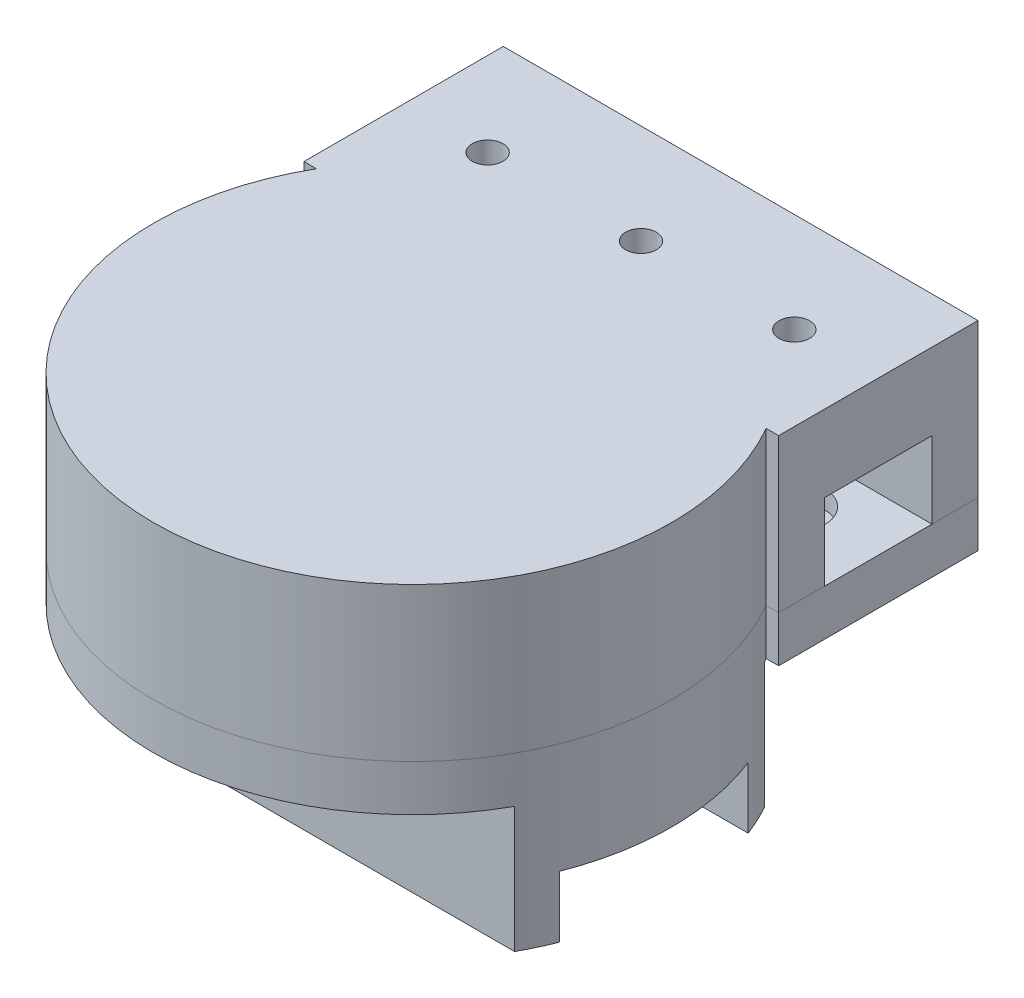
SolidWorks part; units mm, degrees
note: The reader was unsure of these and kept them because the rebuilt part matched: shared geometry of "Sketch1<4>", "Sketch1<7>", "Sketch1<9>", "Sketch3<5>", "Sketch11<4>".
ref_plane "Front Plane" through (0, 0, 0) normal (0, 0, 1) x (1, 0, 0)
ref_plane "Top Plane" through (0, 0, 0) normal (0, 1, 0) x (1, 0, 0)
ref_plane "Right Plane" through (0, 0, 0) normal (1, 0, 0) x (0, 0, -1)
sketch "Sketch1" plane through (0, 0, 0) normal (0, 1, 0) x (1, 0, 0)
  line L0 (-12.478, 11.3978) -> (12.478, 11.3978)
  line L1 (12.478, 11.3978) -> (12.478, 18.3978)
  line L2 (12.478, 18.3978) -> (-12.478, 18.3978)
  line L3 (-12.478, 18.3978) -> (-12.478, 11.3978)
  line L4 (-15.478, 8.3978) -> (15.478, 8.3978)
  line L5 (15.478, 8.3978) -> (15.478, 21.3978)
  line L6 (15.478, 21.3978) -> (-15.478, 21.3978)
  line L7 (-15.478, 21.3978) -> (-15.478, 8.3978)
  line L8 (-9.478, 18.3978) -> (-9.478, 21.3978)
  line L9 (9.478, 18.3978) -> (9.478, 21.3978)
  line L10 (-12.478, 18.3978) -> (-15.478, 18.3978)
  line L11 (-12.478, 11.3978) -> (-15.478, 11.3978)
  line L12 (12.478, 11.3978) -> (15.478, 11.3978)
  line L13 (12.478, 18.3978) -> (15.478, 18.3978)
  line L14 (0, 0) -> (0, 50.4739) construction
  line L15 (15.478, 21.3978) -> (15.478, 74.3978)
  line L16 (15.478, 74.3978) -> (-15.478, 74.3978)
  line L17 (-15.478, 74.3978) -> (-15.478, 21.3978)
  line L18 (-9.478, 21.3978) -> (-9.478, 71.3978)
  line L19 (-9.478, 71.3978) -> (9.478, 71.3978)
  line L20 (9.478, 71.3978) -> (9.478, 21.3978)
  circle A0 centre (0, 0) radius 16.9
  circle A1 centre (0, 0) radius 8.3978 construction
  circle A2 centre (0, 0) radius 13.9
  circle A3 centre (0, 0) radius 2
  point P17 (0, 21.3978)
  dimension "D1" = 3
  dimension "D3" = 3
  dimension "D6" = 27.8
  dimension "D11" = 4
  dimension "D4" = 3
  dimension "D5" = 3
  dimension "D7" = 11.3978
  dimension "D8" = 7
  dimension "D9" = 3
  dimension "D10" = 50
extrude "Boss-Extrude1" add sketch "Sketch1" against normal blind 5 contours L10 L2 L8 L6 L7 | A0 L0 L11 L7 L4 | A0 L4 L5 L12 L0 | L2 L13 L5 L6 L9 | A2 L4 A0 | A2 L0 A0 L4 | A2 L4 A0 L0 | L3
extrude "Boss-Extrude2" add sketch "Sketch1<4>" along normal blind 5 contours A2 L4 A0 | A1 | L4 A2 A1 | L4 A2 L0 | L0 A2 | A2 L0 A0 | A2 L0 A0 L4 | A2 L4 A0 L0 | A0 L4 L5 L6 L9 L2 L1 L0 | L2 L9 L6 L8 | A0 L0 L3 L2 L8 L6 L7 L4 | L14 L4 A2 L0 | L14 L0 A2 | L14 A2 L0 A0 | L14 A0 L0 L1 L2 | L13 L1 L12 L5
sketch "Sketch1<4>" plane through (0, 0, 0) normal (0, 1, 0) x (1, 0, 0) same geometry as "Sketch1"
sketch "Sketch3" plane through (0, -5, 0) normal (0, -1, 0) x (1, 0, 0)
  line L1 (-15.478, -8.3978) -> (-14.6659, -8.3978) construction
  line L2 (15.478, -21.3978) -> (9.478, -21.3978) construction
  line L3 (-9.478, -21.3978) -> (-15.478, -21.3978) construction
  line L4 (-15.478, -8.3978) -> (-14.6659, -8.3978)
  line L5 (14.6659, -8.3978) -> (15.478, -8.3978) construction
  line L6 (14.6659, -8.3978) -> (15.478, -8.3978)
  line L12 (15.478, -21.3978) -> (15.478, -8.3978)
  line L13 (15.478, -21.3978) -> (9.478, -21.3978)
  line L14 (-9.478, -21.3978) -> (-15.478, -21.3978)
  line L16 (9.478, -21.3978) -> (-9.478, -21.3978)
  line L17 (-15.478, -21.3978) -> (-15.478, -8.3978)
  arc A2 (14.6659, -8.3978) -> (-14.6659, -8.3978) centre (0, 0) ccw construction
  arc A3 (14.6659, -8.3978) -> (-14.6659, -8.3978) centre (0, 0) ccw
  circle A4 centre (0, 0) radius 5.35
  circle A5 centre (0, 0) radius 2 construction
  dimension "D2" = 10.7
extrude "Boss-Extrude6" add sketch "Sketch1<7>" along normal up to surface (5 mm away) and the other way blind 2 contours A3 up to face at (0, 5, -8.5148)
sketch "Sketch1<7>" plane through (0, 0, 0) normal (0, 1, 0) x (1, 0, 0) same geometry as "Sketch1"
extrude "Boss-Extrude7" add sketch "Sketch3" along normal blind 3 separate body
sketch "Sketch5" plane through (0, 5, 0) normal (0, 1, 0) x (1, 0, 0)
  line L0 (-15.478, 14.8978) -> (15.478, 14.8978) construction
  line L1 (-15.478, 21.3978) -> (-15.478, 8.3978) construction
  line L2 (15.478, 8.3978) -> (15.478, 21.3978) construction
  line L3 (-5.478, 14.8978) -> (25.478, 14.8978) construction
  line L4 (-25.478, 14.8978) -> (5.478, 14.8978) construction
  circle A0 centre (0, 14.8978) radius 1
  circle A1 centre (10, 14.8978) radius 1
  circle A2 centre (-10, 14.8978) radius 1
  dimension "D1" = 2
  dimension "D2" = 2
extrude "Cut-Extrude1" cut sketch "Sketch5" against normal blind 15
sketch "Sketch6" plane through (0, 0, 0) normal (0, -1, 0) x (1, 0, 0)
  circle A0 centre (10, -14.8978) radius 1 construction
  circle A1 centre (0, -14.8978) radius 1 construction
  circle A2 centre (-10, -14.8978) radius 1 construction
  circle A9 centre (-10, -14.8978) radius 1 construction
  circle A10 centre (0, -14.8978) radius 1 construction
  circle A11 centre (10, -14.8978) radius 1 construction
  circle A12 centre (-10, -14.8978) radius 2
  circle A13 centre (0, -14.8978) radius 2
  circle A14 centre (10, -14.8978) radius 2
  dimension "D1" = 1
extrude "Cut-Extrude2" cut sketch "Sketch6" against normal blind 1 and the other way blind 6.2
extrude "Boss-Extrude9" add sketch "Sketch1<9>" against normal blind 1.6 contours L2 L9 L6 L8
sketch "Sketch1<9>" plane through (0, 0, 0) normal (0, 1, 0) x (1, 0, 0) same geometry as "Sketch1"
extrude "Cut-Extrude3" cut sketch "Sketch3<5>" along normal blind 5 contours A4
sketch "Sketch3<5>" plane through (0, -5, 0) normal (0, -1, 0) x (1, 0, 0) same geometry as "Sketch3"
sketch "Sketch7" [suppressed] plane through (0, 0, 0) normal (0, -1, 0) x (1, 0, 0)
  circle A0 centre (0, 0) radius 5.35
  circle A1 centre (0, 0) radius 2 construction
  dimension "D1" = 10.7
extrude "Cut-Extrude4" [suppressed] cut sketch "Sketch7" against normal blind 5
sketch "Sketch10" [suppressed] plane through (0, -5, 0) normal (0, 1, 0) x (1, 0, 0)
  circle A0 centre (0, 0) radius 2
  circle A1 centre (0, 0) radius 5.35
  circle A2 centre (0, 0) radius 5.35 construction
  dimension "D2" = 4
  dimension "D1" = 0
extrude "Boss-Extrude10" [suppressed] add sketch "Sketch10" along normal blind 2
sketch "Sketch11" plane through (0, -8, 0) normal (0, -1, 0) x (1, 0, 0)
  line L0 (-13.478, -9.8978) -> (13.478, -9.8978) construction
  line L1 (13.478, -9.8978) -> (13.478, -19.8978) construction
  line L2 (13.478, -19.8978) -> (-13.478, -19.8978) construction
  line L3 (-13.478, -19.8978) -> (-13.478, -9.8978) construction
  line L4 (15.478, -21.3978) -> (-15.478, -21.3978) construction
  line L6 (15.478, -21.3978) -> (15.478, -8.3978) construction
  line L8 (-15.478, -21.3978) -> (-15.478, -8.3978) construction
  line L9 (14.6659, -8.3978) -> (15.478, -8.3978) construction
  circle A0 centre (-13.478, -9.8978) radius 0.75
  circle A1 centre (13.478, -9.8978) radius 0.75
  circle A2 centre (13.478, -19.8978) radius 0.75
  circle A3 centre (-13.478, -19.8978) radius 0.75
  circle A4 centre (0, 15.2713) radius 0.75
  circle A5 centre (13.478, -19.8978) radius 1.25
  circle A6 centre (13.478, -9.8978) radius 1.25
  circle A7 centre (-13.478, -19.8978) radius 1.25
  circle A8 centre (-13.478, -9.8978) radius 1.25
  circle A9 centre (0, 15.2713) radius 1.25
  point P12 (15.0719, -8.3978)
  dimension "D1" = 1.5
  dimension "D2" = 1.5
  dimension "D3" = 1.5
  dimension "D5" = 2
  dimension "D6" = 2
  dimension "D4" = 0.5
extrude "Cut-Extrude5" cut sketch "Sketch11" against normal blind 6 contours A2 | A1 | A4 | A0 | A3
sketch "Sketch12" plane through (0, -8, 0) normal (0, -1, 0) x (1, 0, 0)
  line L0 (19.2528, -0.002) -> (-8.75, -0.002) construction
  line L1 (21.2528, -8.15) -> (-10.75, -8.15)
  line L2 (-10.75, 8.15) -> (21.2528, 8.15)
  line L3 (15.9249, 6.15) -> (-9.922, 6.15) construction
  line L4 (13.4662, -6.15) -> (-12.4377, -6.15) construction
  line L5 (21.2528, 8.15) -> (21.2528, 0.498)
  line L6 (21.2528, -0.502) -> (21.2528, -8.15)
  line L7 (-10.75, 8.15) -> (-10.75, 0.498)
  line L8 (-10.75, -0.502) -> (-10.75, -8.15)
  line L9 (-9.8956, -0.502) -> (-10.75, -0.502)
  line L10 (-10.75, 0.498) -> (-9.8956, 0.498)
  line L11 (5.75, 2.5) -> (5.1781, 2.5) construction
  line L12 (5.1781, -2.5) -> (5.75, -2.5) construction
  line L13 (5.1781, 2.5) -> (5.75, 2.5) construction
  line L14 (5.75, -2.5) -> (5.1781, -2.5) construction
  line L15 (20.3985, 0.498) -> (21.2528, 0.498)
  line L16 (21.2528, -0.502) -> (20.3985, -0.502)
  line L17 (5.75, 2.9) -> (5.4233, 2.9)
  line L18 (5.4233, -2.9) -> (5.75, -2.9)
  arc A0 (-9.8956, -0.502) -> (-9.8956, 0.498) centre (-8.75, -0.002) ccw
  arc A1 (0, 5.75) -> (-5.75, 0) centre (0, 0) ccw construction
  arc A2 (5.75, -2.5) -> (5.75, 2.5) centre (5.75, 0) ccw construction
  arc A3 (5.1781, 2.5) -> (5.1781, -2.5) centre (0, 0) ccw construction
  arc A4 (0, -5.75) -> (5.1781, -2.5) centre (0, 0) ccw construction
  arc A5 (5.1781, 2.5) -> (0, 5.75) centre (0, 0) ccw construction
  arc A6 (5.75, -2.5) -> (5.75, 2.5) centre (5.75, 0) ccw construction
  arc A7 (20.3985, 0.498) -> (20.3985, -0.502) centre (19.2528, -0.002) ccw
  arc A8 (5.4233, 2.9) -> (5.4233, -2.9) centre (0, 0) ccw
  arc A9 (5.75, -2.9) -> (5.75, 2.9) centre (5.75, 0) ccw
  circle A10 centre (0, 0) radius 2 construction
  arc A13 (14.6659, -8.3978) -> (-14.6659, -8.3978) centre (0, 0) ccw construction
  arc A14 (14.805, -8.15) -> (14.805, 8.15) centre (0, 0) ccw
extrude "Boss-Extrude11" add sketch "Sketch12" along normal blind 4.2
sketch "Sketch13" plane through (0, -12.2, 0) normal (0, -1, 0) x (1, 0, 0)
  line L0 (14.805, -8.15) -> (-10.75, -8.15) construction
  line L1 (-10.75, -0.502) -> (-10.75, -8.15) construction
  line L2 (-10.75, 8.15) -> (-10.75, 0.498) construction
  line L3 (-10.75, 0.498) -> (-9.8956, 0.498) construction
  line L4 (-10.75, 8.15) -> (14.805, 8.15) construction
  line L5 (-9.8956, -0.502) -> (-10.75, -0.502) construction
  line L6 (5.75, 2.9) -> (5.4233, 2.9) construction
  line L7 (5.4233, -2.9) -> (5.75, -2.9) construction
  line L8 (14.805, -8.15) -> (-10.75, -8.15)
  line L9 (-10.75, -0.502) -> (-10.75, -8.15)
  line L10 (-10.75, 8.15) -> (-10.75, 0.498)
  line L11 (-10.75, 0.498) -> (-9.8956, 0.498)
  line L12 (-10.75, 8.15) -> (14.805, 8.15)
  line L13 (-9.8956, -0.502) -> (-10.75, -0.502)
  line L14 (5.75, 2.9) -> (5.4233, 2.9)
  line L15 (5.4233, -2.9) -> (5.75, -2.9)
  line L16 (15.7413, -6.15) -> (-10.75, -6.15)
  line L17 (15.7413, 6.15) -> (-10.75, 6.15)
  arc A0 (-9.8956, -0.502) -> (-9.8956, 0.498) centre (-8.75, -0.002) ccw construction
  arc A2 (5.4233, 2.9) -> (5.4233, -2.9) centre (0, 0) ccw construction
  arc A3 (5.75, -2.9) -> (5.75, 2.9) centre (5.75, 0) ccw construction
  arc A4 (-9.8956, -0.502) -> (-9.8956, 0.498) centre (-8.75, -0.002) ccw
  arc A5 (14.805, -8.15) -> (14.805, 8.15) centre (0, 0) ccw construction
  arc A6 (5.4233, 2.9) -> (5.4233, -2.9) centre (0, 0) ccw
  arc A7 (5.75, -2.9) -> (5.75, 2.9) centre (5.75, 0) ccw
  arc A8 (14.805, -8.15) -> (14.805, 8.15) centre (0, 0) ccw
extrude "Boss-Extrude12" add sketch "Sketch13" along normal blind 4
extrude "Cut-Extrude6" cut sketch "Sketch11<4>" against normal blind 1 contours A5 A2 | A6 A1 | A8 A0 | A7 A3 | A9 A4
sketch "Sketch11<4>" plane through (0, -8, 0) normal (0, -1, 0) x (1, 0, 0) same geometry as "Sketch11"
sketch "Sketch14" [suppressed] plane through (0, 3, 0) normal (0, 1, 0) x (1, 0, 0)
  line L2 (5.4233, -2.9) -> (5.75, -2.9)
  line L3 (5.75, 2.9) -> (5.4233, 2.9)
  line L4 (5.4233, -2.9) -> (5.75, -2.9)
  line L5 (5.75, 2.9) -> (5.4233, 2.9)
  line L10 (21.2528, -8.15) -> (21.2528, -0.498)
  line L11 (-10.75, -8.15) -> (21.2528, -8.15)
  line L12 (-10.75, -0.498) -> (-10.75, -8.15)
  line L13 (-9.8956, -0.498) -> (-10.75, -0.498)
  line L14 (-10.75, 0.502) -> (-9.8956, 0.502)
  line L15 (-10.75, 8.15) -> (-10.75, 0.502)
  line L16 (21.2528, 8.15) -> (-10.75, 8.15)
  line L17 (21.2528, 0.502) -> (21.2528, 8.15)
  line L18 (20.3985, 0.502) -> (21.2528, 0.502)
  line L19 (21.2528, -0.498) -> (20.3985, -0.498)
  line L20 (21.2528, -8.15) -> (21.2528, -0.498)
  line L21 (-10.75, -8.15) -> (21.2528, -8.15)
  line L22 (-10.75, -0.498) -> (-10.75, -8.15)
  line L23 (-9.8956, -0.498) -> (-10.75, -0.498)
  line L24 (-10.75, 0.502) -> (-9.8956, 0.502)
  line L25 (-10.75, 8.15) -> (-10.75, 0.502)
  line L26 (21.2528, 8.15) -> (-10.75, 8.15)
  line L27 (21.2528, 0.502) -> (21.2528, 8.15)
  line L28 (20.3985, 0.502) -> (21.2528, 0.502)
  line L29 (21.2528, -0.498) -> (20.3985, -0.498)
  arc A0 (14.805, -8.15) -> (14.805, 8.15) centre (0, 0) ccw construction
  arc A1 (14.805, -8.15) -> (14.805, 8.15) centre (0, 0) ccw
  arc A2 (-9.8956, -0.498) -> (-9.8956, 0.502) centre (-8.75, 0.002) ccw
  arc A3 (20.3985, 0.502) -> (20.3985, -0.498) centre (19.2528, 0.002) ccw
  arc A4 (-9.8956, -0.498) -> (-9.8956, 0.502) centre (-8.75, 0.002) ccw
  arc A5 (20.3985, 0.502) -> (20.3985, -0.498) centre (19.2528, 0.002) ccw
  arc A6 (5.4233, 2.9) -> (5.4233, -2.9) centre (0, 0) ccw
  arc A7 (5.75, -2.9) -> (5.75, 2.9) centre (5.75, 0) ccw
  arc A8 (5.4233, 2.9) -> (5.4233, -2.9) centre (0, 0) ccw
  arc A9 (5.75, -2.9) -> (5.75, 2.9) centre (5.75, 0) ccw
  dimension "D1" = 0
  dimension "D2" = 0
sketch "Sketch15" plane through (0, 0, -21.3978) normal (0, 0, -1) x (-1, 0, 0)
  line L0 (1, 5) -> (-1, 5) construction
  line L1 (1, 5) -> (-1, 5) construction
  line L2 (0, 5) -> (0, 2.3387) construction
  circle A0 centre (0, 2.3387) radius 1
  circle A1 centre (10, 2.3387) radius 1
  circle A2 centre (-10, 2.3387) radius 1
  dimension "D1" = 2
  dimension "D2" = 2
  dimension "D3" = 2
extrude "Cut-Extrude7" cut sketch "Sketch15" against normal blind 3
